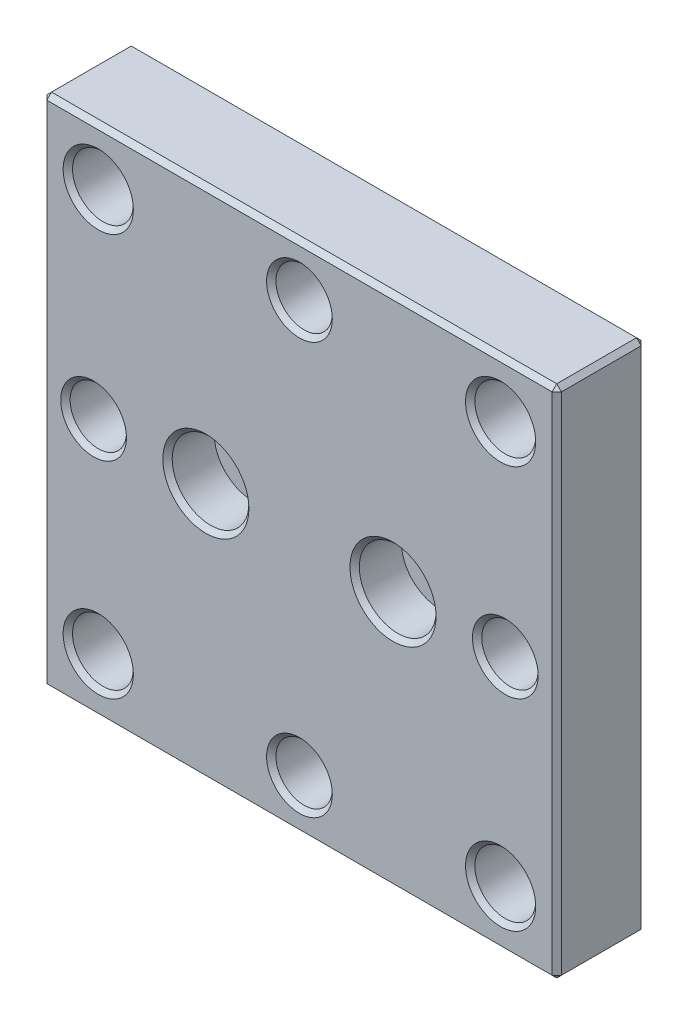
SolidWorks part; units mm, degrees
ref_plane "Front Plane" through (0, 0, 0) normal (0, 0, 1) x (1, 0, 0)
ref_plane "Top Plane" through (0, 0, 0) normal (0, 1, 0) x (1, 0, 0)
ref_plane "Right Plane" through (0, 0, 0) normal (1, 0, 0) x (0, 0, -1)
sketch "Sketch1" plane through (0, 0, 0) normal (0, 0, 1) x (1, 0, 0)
  line L1 (0, 0) -> (55, 0)
  line L2 (0, 0) -> (0, 55)
  line L3 (0, 55) -> (55, 55)
  line L4 (55, 0) -> (55, 55)
  circle A0 centre (27.5, 27.5) radius 15.125 construction
  circle A1 centre (17.5, 27.5) radius 2.2
  circle A2 centre (37.5, 27.5) radius 2.2
  circle A3 centre (17.5, 27.5) radius 4.1
  circle A4 centre (37.5, 27.5) radius 4.1
  dimension "D5" = 30.25
  dimension "D6" = 4.4
  dimension "D7" = 4.4
  dimension "D10" = 8.2
  dimension "D11" = 8.2
  dimension "D1" = 55
  dimension "D2" = 55
  dimension "D3" = 27.5
  dimension "D4" = 27.5
  dimension "D8" = 10
  dimension "D9" = 10
extrude "Boss-Extrude1" add sketch "Sketch1" along normal blind 9.525 contours L1 L4 L3 L2 A4 A3 region at (27.5, 27.5, 0)
extrude "Boss-Extrude2" add sketch "Sketch1<3>" along normal blind 4.525 contours A3 A1 | A4 A2 region at (13.516, 27.5, 0) region at (33.516, 27.5, 0)
sketch "Sketch1<3>" plane through (0, 0, 0) normal (0, 0, 1) x (1, 0, 0) same geometry as "Sketch1"
sketch "Sketch3" plane through (0, 0, 9.525) normal (0, 0, 1) x (1, 0, 0)
  line L0 (0, 55) -> (55, 55) construction
  line L1 (0, 0) -> (0, 55) construction
  line L2 (0, 0) -> (55, 0) construction
  line L3 (55, 0) -> (55, 55) construction
  circle A0 centre (27.5, 49.5) radius 3.0127
  circle A1 centre (5.5, 27.5) radius 3.0127
  circle A2 centre (49.5, 27.5) radius 3.0127
  circle A3 centre (27.5, 5.5) radius 3.0127
  dimension "D6" = 6.0254
  dimension "D7" = 6.0254
  dimension "D8" = 6.0254
  dimension "D9" = 6.0254
  dimension "D1" = 27.5
  dimension "D2" = 27.5
  dimension "D3" = 27.5
  dimension "D4" = 27.5
  dimension "D5" = 5.5
  dimension "D10" = 5.5
  dimension "D11" = 5.5
  dimension "D12" = 5.5
extrude "Cut-Extrude1" cut sketch "Sketch3" against normal through all
sketch "Sketch5" plane through (0, 0, 9.525) normal (0, 0, 1) x (1, 0, 0)
  line L0 (0, 55) -> (55, 55) construction
  line L1 (0, 0) -> (0, 55) construction
  circle A0 centre (6, 49) radius 3.2512
  circle A1 centre (49, 49) radius 3.2512
  circle A2 centre (49, 6) radius 3.2512
  circle A3 centre (6, 6) radius 3.2512
  dimension "D1" = 6.5024
  dimension "D2" = 6.5024
  dimension "D3" = 6.5024
  dimension "D4" = 6.5024
  dimension "D5" = 6
  dimension "D6" = 6
  dimension "D7" = 43
  dimension "D8" = 43
extrude "Cut-Extrude2" cut sketch "Sketch5" against normal blind 6.4008
chamfer "Chamfer1" distance 0.5 angle 45 28 edges at (52.5127, 27.5, 0) (39.7, 27.5, 0) (30.5127, 49.5, 0) (30.5127, 5.5, 0) (19.7, 27.5, 0) (8.5127, 27.5, 0) (9.2512, 49, 9.525) (9.2512, 6, 9.525) (8.5127, 27.5, 9.525) (21.6, 27.5, 9.525) (41.6, 27.5, 9.525) (30.5127, 5.5, 9.525) (52.2512, 6, 9.525) (52.5127, 27.5, 9.525) (52.2512, 49, 9.525) (30.5127, 49.5, 9.525) (27.5, 55, 0) (55, 55, 4.7625) (55, 27.5, 0) (55, 0, 4.7625) (27.5, 0, 0) (0, 27.5, 0) (0, 55, 4.7625) (0, 0, 4.7625) (55, 27.5, 9.525) (27.5, 0, 9.525) (0, 27.5, 9.525) (27.5, 55, 9.525)
sketch "Sketch6" plane through (0, 0, 9.525) normal (0, 0, 1) x (1, 0, 0)
  circle A0 centre (6, 49) radius 1.25
  circle A1 centre (49, 49) radius 1.25
  circle A2 centre (49, 6) radius 1.25
  circle A3 centre (6, 6) radius 1.25
  dimension "D1" = 2.5
  dimension "D2" = 2.5
  dimension "D3" = 2.5
  dimension "D4" = 2.5
extrude "Cut-Extrude3" cut sketch "Sketch6" against normal through all
chamfer "Chamfer2" distance 0.5 angle 45 8 edges at (7.25, 6, 3.1242) (50.25, 6, 3.1242) (50.25, 49, 3.1242) (7.25, 49, 3.1242) (7.25, 49, 0) (50.25, 49, 0) (50.25, 6, 0) (7.25, 6, 0)
